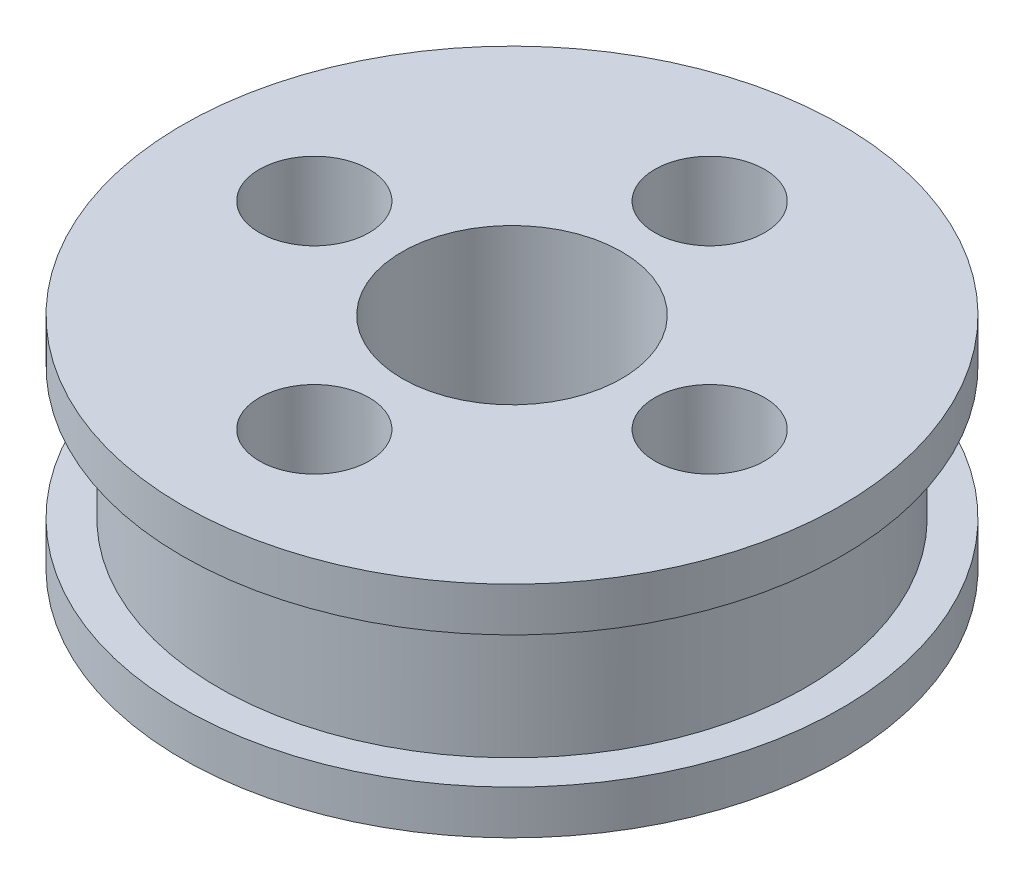
SolidWorks part; units mm, degrees
ref_plane "Front Plane" through (0, 0, 0) normal (0, 0, 1) x (1, 0, 0)
ref_plane "Top Plane" through (0, 0, 0) normal (0, 1, 0) x (1, 0, 0)
ref_plane "Right Plane" through (0, 0, 0) normal (1, 0, 0) x (0, 0, -1)
sketch "Sketch1" plane through (0, 0, 0) normal (0, 1, 0) x (1, 0, 0)
  circle A0 centre (0, 0) radius 13.365
  dimension "D1" = 26.73
extrude "Boss-Extrude1" add sketch "Sketch1" along normal blind 10
sketch "Sketch2" plane through (0, 10, 0) normal (0, 1, 0) x (1, 0, 0)
  circle A0 centre (0, 0) radius 15
  dimension "D1" = 30
extrude "Boss-Extrude2" add sketch "Sketch2" against normal blind 2
sketch "Sketch3" plane through (0, 0, 0) normal (0, -1, 0) x (1, 0, 0)
  circle A0 centre (0, 0) radius 15
  dimension "D1" = 30
extrude "Boss-Extrude3" add sketch "Sketch3" against normal blind 2
sketch "Sketch4" plane through (0, 0, 0) normal (0, -1, 0) x (1, 0, 0)
  circle A0 centre (0, 0) radius 5
  circle A1 centre (0, 0) radius 9
  circle A2 centre (0, 9) radius 2.5
  circle A3 centre (9, 0) radius 2.5
  circle A4 centre (0, -9) radius 2.5
  circle A5 centre (-9, 0) radius 2.5
  point P15 (0, 0)
  dimension "D1" = 5
  dimension "D2" = 18
  dimension "D3" = 10
  dimension "D4" = 4
extrude "Cut-Extrude1" cut sketch "Sketch4" against normal through all and the other way blind 10 contours A1 A2 | A1 A2 | A1 A5 | A1 A5 | A1 A4 | A1 A4 | A1 A3 | A1 A3 | A0 region at (0, 0, 0) region at (7.8789, 0, 0) region at (9.996, 0, 0) region at (0, 0, 7.8789) region at (0, 0, 9.996) region at (0, 0, -9.996) region at (0, 0, -7.8789) region at (-7.8789, 0, 0) region at (-9.996, 0, 0)
